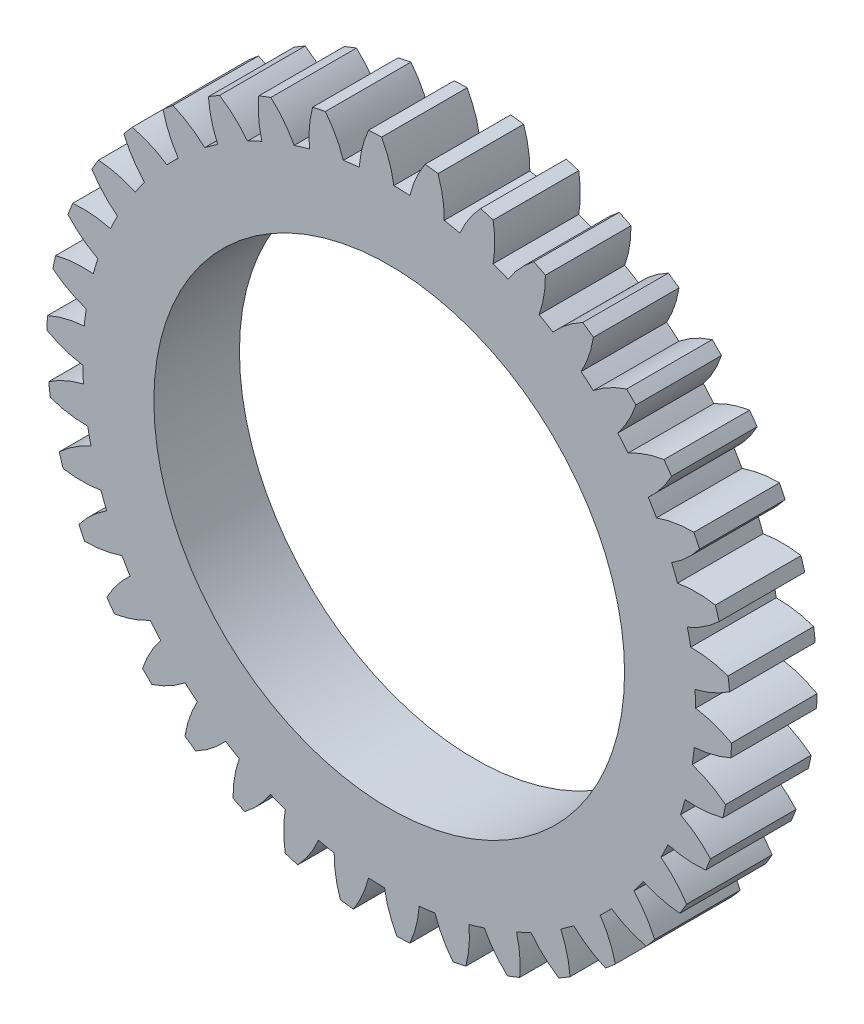
SolidWorks part; units mm, degrees
ref_plane "Front Plane" through (0, 0, 0) normal (0, 0, 1) x (1, 0, 0)
ref_plane "Top Plane" through (0, 0, 0) normal (0, 1, 0) x (1, 0, 0)
ref_plane "Right Plane" through (0, 0, 0) normal (1, 0, 0) x (0, 0, -1)
sketch "Construction" plane through (0, 0, 0) normal (0, 0, 1) x (1, 0, 0)
  line L0 (0, 0) -> (0, 62.6994) construction
  line L1 (-27.5436, 38) -> (27.5436, 38) construction
  line L2 (-24.5413, 29.0677) -> (24.5413, 46.9323) construction
  line L3 (0, 0) -> (-12.213, 33.5548) construction
  line L4 (-12.213, 33.5548) -> (0, 38) construction
  line L5 (-17.2163, 31.2839) -> (0, 0) construction
  line L6 (-17.2163, 31.2839) -> (-1.0113, 40.2019) construction
  line L7 (-4.4529, 35.4296) -> (0, 0) construction
  line L8 (-4.4529, 35.4296) -> (0.5048, 36.0527) construction
  line L9 (0, 0) -> (-2.5678, 62.0841) construction
  circle A0 centre (0, 0) radius 38 construction
  circle A1 centre (0, 0) radius 35.7083 construction
  arc A2 (-12.213, 33.5548) -> (-17.2163, 31.2839) centre (0, 0) ccw
  arc A3 (-12.213, 33.5548) -> (-4.4529, 35.4296) centre (0, 0) cw construction
  point P6 (0, 38)
  point P9 (0, 38)
  dimension "D1" = 76
  dimension "D2" = 20
  dimension "D3" = 12.9968
  dimension "D5" = 18.4968
  dimension "D7" = 4.9968
  dimension "D8" = 2.368
  dimension "D4" = 5.5
  dimension "D6" = 8
sketch "Tooth" plane through (0, 0, 0) normal (0, 0, 1) x (1, 0, 0)
  line L0 (-27.5436, 38) -> (27.5436, 38) construction
  line L1 (0, 0) -> (-2.6697, 64.5478) construction
  line L2 (0, 0) -> (0, 62.6994) construction
  line L3 (-1.4808, 35.8027) -> (1.0093, 35.8027) construction
  line L4 (0.5048, 36.0527) -> (-1.4912, 36.0527) construction
  circle A0 centre (0, 0) radius 40 construction
  circle A1 centre (0, 0) radius 35.8069 construction
  spline S0 degree 3 poles (0.5464, 35.8027) (0.5333, 35.8863) (0.274, 37.4453) (-0.2599, 38.9064) (-1.0113, 40.2019) knots -0.056473 -0.056473 -0.056473 -0.056473 0 1 1 1 1
  spline S1 degree 3 poles (-3.5011, 35.6353) (-3.495, 35.7197) (-3.3653, 37.2947) (-2.9538, 38.795) (-2.312, 40.1481) knots -0.056473 -0.056473 -0.056473 -0.056473 0 1 1 1 1
  dimension "D2" = 80
  dimension "D1" = 2.368
  dimension "D3" = 0.25
sketch "Gear" plane through (0, 0, 0) normal (0, 0, 1) x (1, 0, 0)
  circle A0 centre (0, 0) radius 35.8069 construction
  circle A1 centre (0, 0) radius 40 construction
  circle A2 centre (0, 0) radius 35.8069
  arc A3 (-0.8911, 39.9901) -> (-2.4143, 39.9271) centre (0, 0) ccw
  spline S0 degree 3 poles (-2720.322, -1220.0591) (-890.5547, -472.7225) (937.4564, 371.2061) (-983.5521, -119.9481) (-2903.2707, -706.3706) knots -61.244588 -61.244588 -61.244588 -61.244588 0 62.19832 62.19832 62.19832 62.19832 only from (0.5464, 35.8027) to (-1.0113, 40.2019) construction
  spline S1 degree 3 poles (4722.7795, -1580.865) (1561.0806, -620.9149) (-1608.7158, 463.4032) (1643.1819, -156.729) (4903.5268, -899.8713) knots -79.273123 -79.273123 -79.273123 -79.273123 0 80.226645 80.226645 80.226645 80.226645 only from (-3.5011, 35.6353) to (-2.312, 40.1481) construction
  spline S2 degree 3 poles (0.5464, 35.8027) (0.5333, 35.8863) (0.2873, 37.3651) (-0.2058, 38.756) (-0.8911, 39.9901) knots -0.056473 -0.056473 -0.056473 -0.056473 0 0.945698 0.945698 0.945698 0.945698
  spline S3 degree 3 poles (-3.5011, 35.6353) (-3.495, 35.7197) (-3.3719, 37.2138) (-2.9954, 38.6406) (-2.4143, 39.9271) knots -0.056473 -0.056473 -0.056473 -0.056473 0 0.945698 0.945698 0.945698 0.945698
  spline S4 degree 3 poles (-3.5011, 35.6353) (-3.495, 35.7197) (-3.3719, 37.2138) (-2.9954, 38.6406) (-2.4143, 39.9271) knots -0.056473 -0.056473 -0.056473 -0.056473 0 0.945698 0.945698 0.945698 0.945698
extrude "body" add sketch "Gear" along normal blind 10 contours A2 region at (0, 0, 0)
extrude "ToothExtrude" add sketch "Gear<3>" along normal blind 10 contours S3 A2 S2 A3 region at (-1.554, 37.5725, 0)
sketch "Gear<3>" plane through (0, 0, 0) normal (0, 0, 1) x (1, 0, 0) same geometry as "Gear"
pattern_circular "CirPattern1" count 38 over 360 about axis through (0, 0, 10) along (0, 0, -1) of "ToothExtrude" reverse direction yes
sketch "Sketch5" plane through (0, 0, 10) normal (0, 0, 1) x (1, 0, 0)
  circle A0 centre (0, 0) radius 27.5
  dimension "D1" = 55
extrude "Cut-Extrude1" cut sketch "Sketch5" against normal through all
equation "\"D5@Construction\" = \"D3@Construction\" + \"D4@Construction\""
equation "\"D7@Construction\" = \"D3@Construction\" - \"D6@Construction\""
